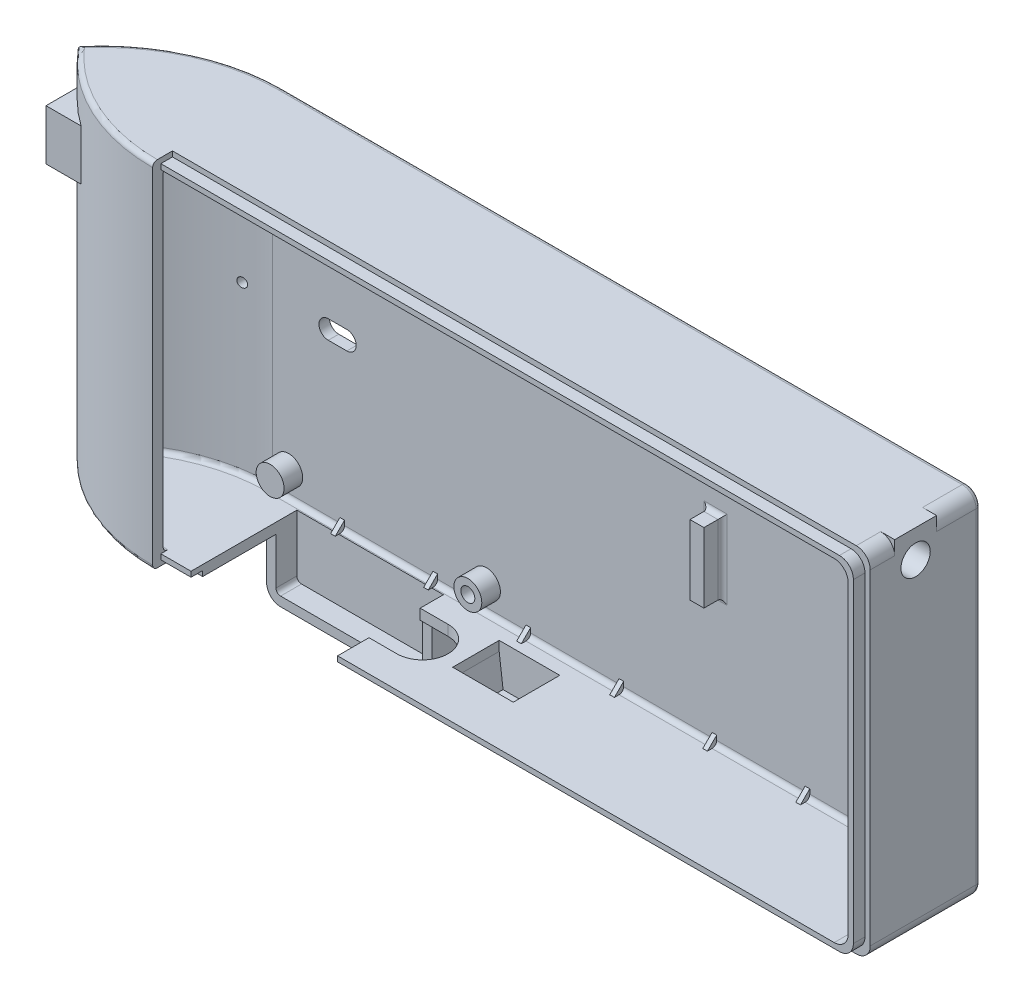
SolidWorks part; units mm, degrees
ref_plane "Front Plane" through (0, 0, 0) normal (0, 0, 1) x (1, 0, 0)
ref_plane "Top Plane" through (0, 0, 0) normal (0, 1, 0) x (1, 0, 0)
ref_plane "Right Plane" through (0, 0, 0) normal (1, 0, 0) x (0, 0, -1)
sketch "Sketch1" plane through (0, 0, 0) normal (0, 1, 0) x (1, 0, 0)
  line L0 (0, 14) -> (-30, 14) construction
  line L1 (0, 0) -> (150, 0)
  line L2 (0, 0) -> (0, 28) construction
  line L3 (0, 28) -> (150, 28)
  line L4 (150, 0) -> (150, 28)
  line L5 (0, 0) -> (150, 28) construction
  line L6 (0, 28) -> (150, 0) construction
  arc A0 (-30, 14) -> (0, 28) centre (0, -11.1429) cw
  arc A1 (-30, 14) -> (0, 0) centre (0, 39.1429) ccw
  point P4 (75, 14)
  point P9 (0, 14)
  dimension "D1" = 30
  dimension "D2" = 28
  dimension "D3" = 150
extrude "Boss-Extrude1" add sketch "Sketch1" along normal blind 38
sketch "Sketch3" plane through (0, 0, 0) normal (0, -1, 0) x (1, 0, 0)
  line L8 (0, -2.25) -> (0, 0)
  line L9 (0, 0) -> (147.75, 0)
  line L10 (0, 0) -> (150, 0) construction
  line L11 (147.75, -25.75) -> (147.75, -2.25)
  line L12 (0, -25.75) -> (147.75, -25.75)
  line L13 (147.75, -2.25) -> (0, -2.25)
  line L15 (0, -25.75) -> (147.75, -25.75)
  line L18 (147.75, 0) -> (147.75, -25.75)
  arc A9 (-26.9985, -14) -> (0, -25.75) centre (0, 11.1429) ccw
  arc A10 (0, -2.25) -> (-26.9985, -14) centre (0, -39.1429) ccw
  arc A11 (-26.9985, -14) -> (0, -25.75) centre (0, 11.1429) ccw
  arc A12 (0, -2.25) -> (-26.9985, -14) centre (0, -39.1429) ccw
  dimension "D1" = 2.25
extrude "Cut-Extrude1" cut sketch "Sketch3" against normal blind 35.75
ref_plane "Plane1" through (75, 0, 0) normal (1, 0, 0) x (0, 0, -1)
sketch "Sketch4" plane through (75, 0, 0) normal (1, 0, 0) x (0, 0, -1)
  line L0 (23.75, 35.75) -> (25.75, 33.75)
  line L1 (14, 35.75) -> (25.75, 35.75) construction
  line L2 (25.75, 35.75) -> (25.75, 0) construction
  dimension "D1" = 2
  dimension "D2" = 2
rib "Rib6" sketch "Sketch4" sketch "Sketch4" thickness 1 extrusion direction parallel to sketch draft on no parameters "D1"=1
pattern_linear "LPattern2" count 4 spacing 20 along (-1, 0, 0) count 4 spacing 20 along (1, 0, 0) of "Rib6" pattern seed only yes
ref_plane "Plane2" through (0, 20, 0) normal (0, -1, 0) x (-1, 0, 0)
sketch "Sketch5" plane through (0, 20, 0) normal (0, -1, 0) x (1, 0, 0)
  line L0 (145.75, -25.75) -> (147.75, -23.75)
  line L1 (0, -25.75) -> (147.75, -25.75) construction
  line L2 (147.75, -25.75) -> (147.75, 0) construction
  line L3 (135.5, -25.75) -> (147.75, -25.75) construction
  dimension "D1" = 2
  dimension "D2" = 2
rib "Rib8" sketch "Sketch5" sketch "Sketch5" thickness 1 extrusion direction parallel to sketch draft on no parameters "D1"=1
mirror "Mirror1" about plane through (0, 0, -39.1429) normal (0, 1, 0) of bodies 103
sketch "Sketch7" plane through (0, 0, 0) normal (0, 0, 1) x (1, 0, 0)
  line L5 (0, 38) -> (150, 38)
  line L6 (150, 38) -> (150, -38)
  line L9 (150, -38) -> (0, -38)
  line L15 (0, -38) -> (0, -36.875)
  line L16 (0, -38) -> (0, -35.75) construction
  line L17 (0, -36.875) -> (148.875, -36.875)
  line L18 (148.875, -36.875) -> (148.875, 36.875)
  line L19 (148.875, 36.875) -> (0, 36.875)
  line L20 (0, 38) -> (0, 35.75) construction
  line L22 (0, 38) -> (0, 36.875)
  dimension "D1" = 1.125
  dimension "D2" = 1.125
  dimension "0.8" = 1.125
extrude "Clam shell lip" cut sketch "Sketch7" against normal blind 4.25
fillet "Fillet7" radius 3 6 edges at (147.75, 35.75, -12.875) (150, 38, -16.125) (150, -38, -16.125) (147.75, -35.75, -12.875) (148.875, -36.875, -2.125) (148.875, 36.875, -2.125)
sketch "Sketch9" plane through (0, 0, 0) normal (0, 0, 1) x (1, 0, 0)
  line L0 (0, -38) -> (147, -38) construction
  line L1 (0, 38) -> (150, 38)
  line L2 (0, 38) -> (0, -38)
  line L3 (0, -38) -> (150, -38)
  line L4 (150, 38) -> (150, -38)
  line L5 (0, 38) -> (150, -38) construction
  line L6 (0, -38) -> (150, 38) construction
  line L7 (150, -35) -> (150, 35) construction
  line L8 (147, 38) -> (0, 38) construction
  point P4 (75, 0)
extrude "Cut-Extrude4" cut sketch "Sketch9" against normal blind 1.75
sketch "Sketch10" plane through (150, 0, 0) normal (1, 0, 0) x (0, 0, -1)
  line L0 (28, 35) -> (28, -35) construction
  line L1 (4.25, 38) -> (28, 38) construction
  line L2 (9.5, 32) -> (9.5, 38)
  line L3 (9.5, 38) -> (18.5, 38)
  line L4 (18.5, 38) -> (18.5, 32)
  arc A0 (9.5, 32) -> (18.5, 32) centre (14, 32) ccw
  dimension "D1" = 9
  dimension "D2" = 14
  dimension "D3" = 6
extrude "Arrow Shaft Extrude" add sketch "Sketch10" against normal blind 50
sketch "Sketch11" plane through (150, 0, 0) normal (1, 0, 0) x (0, 0, -1)
  circle A0 centre (14, 32) radius 3.15
  dimension "D1" = 6.3
extrude "Arrow Shaft Ex-Cut" cut sketch "Sketch11" against normal up to surface (50 mm away) up to face at (100, 32.75, -14)
sketch "Sketch12" plane through (0, 0, -25.75) normal (0, 0, 1) x (1, 0, 0)
  line L0 (35.5, -35.75) -> (54.5, -35.75) construction
  line L1 (0, 35.75) -> (0, -35.75) construction
  line L2 (3.5, 19.66) -> (3.5, -30.34) construction
  line L3 (3.5, -30.34) -> (46, -30.34) construction
  line L4 (3.5, 19.66) -> (78.5, 19.66) construction
  circle A0 centre (46, -30.34) radius 1.5
  circle A1 centre (3.5, 19.66) radius 1.5
  circle A2 centre (46, -30.34) radius 3
  circle A3 centre (3.5, 19.66) radius 3
  circle A4 centre (3.5, -30.34) radius 3
  circle A5 centre (78.5, 19.66) radius 3
  dimension "D1" = 3
  dimension "D3" = 6
  dimension "D2" = 5.41
  dimension "D4" = 42.5
  dimension "D5" = 50
  dimension "D6" = 46
  dimension "D7" = 75
extrude "PCB Studs" add sketch "Sketch12" along normal blind 4
sketch "Sketch13" plane through (0, -38, 0) normal (0, -1, 0) x (1, 0, 0)
  line L1 (6.5, -1.75) -> (38, -1.75)
  line L2 (6.5, -1.75) -> (6.5, -24.5)
  line L3 (6.5, -24.5) -> (38, -24.5)
  line L4 (38, -1.75) -> (38, -8.5)
  line L5 (6.5, -1.75) -> (38, -24.5) construction
  line L6 (6.5, -24.5) -> (38, -1.75) construction
  line L7 (0, -4.25) -> (0, 0) construction
  line L8 (147, -28) -> (0, -28) construction
  line L9 (-30, -14) -> (150, -14) construction
  line L10 (150, -4.25) -> (150, -28) construction
  line L11 (44, -8.5) -> (38, -8.5)
  line L12 (44, -19.5) -> (38, -19.5)
  line L13 (38, -19.5) -> (38, -24.5)
  line L14 (0, -1.75) -> (145.875, -1.75) construction
  arc A0 (44, -19.5) -> (44, -8.5) centre (44, -14) ccw
  point P4 (22.25, -13.125)
  dimension "D4" = 11
  dimension "D1" = 6.5
  dimension "D2" = 3.5
  dimension "D3" = 31.5
  dimension "D5" = 6
extrude "SHT-PCB " cut sketch "Sketch13" against normal up to surface (2.25 mm away) up to face at (69.4134, -35.75, -22.4779)
sketch "Sketch14" plane through (0, -38, 0) normal (0, -1, 0) x (1, 0, 0)
  line L5 (147, -28) -> (0, -28) construction
  line L6 (4.5, -20) -> (40, -20)
  line L9 (4.5, -20) -> (4.5, -28)
  line L10 (4.5, -28) -> (40, -28)
  line L11 (40, -20) -> (40, -28)
  line L12 (4.5, -20) -> (40, -28) construction
  line L13 (4.5, -28) -> (40, -20) construction
  line L14 (38, -24.5) -> (38, -19.5) construction
  line L15 (6.5, -4.25) -> (6.5, -24.5) construction
  point P4 (22.25, -24)
  dimension "D1" = 8
  dimension "D2" = 2
  dimension "D3" = 2
extrude "PCB extension" add sketch "Sketch14" along normal blind 13
fillet "Fillet1" radius 3 2 edges at (40, -51, -24) (4.5, -51, -24)
sketch "Sketch15" plane through (0, 0, -20) normal (0, 0, 1) x (1, 0, 0)
  line L0 (6.5, -40) -> (6.5, -38)
  line L1 (38, -40) -> (38, -38)
  line L2 (38, -38) -> (6.5, -38)
  line L12 (7.5, -49) -> (37, -49)
  line L13 (38, -48) -> (38, -40)
  line L14 (38, -40) -> (6.5, -40)
  line L15 (6.5, -40) -> (6.5, -48)
  line L16 (7.5, -49) -> (37, -49)
  line L17 (38, -48) -> (38, -40)
  line L19 (6.5, -40) -> (6.5, -48)
  arc A4 (37, -49) -> (38, -48) centre (37, -48) ccw
  arc A5 (6.5, -48) -> (7.5, -49) centre (7.5, -48) ccw
  arc A6 (37, -49) -> (38, -48) centre (37, -48) ccw
  arc A7 (6.5, -48) -> (7.5, -49) centre (7.5, -48) ccw
  dimension "D1" = 2
extrude "Cut-Extrude7" cut sketch "Sketch15" against normal up to surface (4.5 mm away) up to face at (23.625, -36.3125, -24.5)
ref_plane "Plane3" through (-30, 0, 0) normal (1, 0, 0) x (0, 0, -1)
sketch "Sketch16" plane through (-30, 0, 0) normal (1, 0, 0) x (0, 0, -1)
  line L0 (14, 38) -> (14, -38) construction
  line L1 (18.925, 28) -> (9.075, 28)
  line L2 (18.925, 28) -> (18.925, 21.15)
  line L3 (18.925, 21.15) -> (9.075, 21.15)
  line L4 (9.075, 28) -> (9.075, 21.15)
  line L5 (18.925, 28) -> (9.075, 21.15) construction
  line L6 (18.925, 21.15) -> (9.075, 28) construction
  line L7 (14, 38) -> (0, 38) construction
  point P4 (14, 24.575)
  dimension "D1" = 9.85
  dimension "D2" = 6.85
  dimension "D3" = 10
extrude "Anemometer Shaft" cut sketch "Sketch16" along normal blind 10
sketch "Sketch17" plane through (-30, 0, 0) normal (1, 0, 0) x (0, 0, -1)
  line L6 (14, 38) -> (14, 28) construction
  line L7 (20.925, 30) -> (7.075, 30)
  line L8 (20.925, 30) -> (20.925, 19.15)
  line L9 (20.925, 19.15) -> (7.075, 19.15)
  line L10 (7.075, 30) -> (7.075, 19.15)
  line L11 (20.925, 30) -> (7.075, 19.15) construction
  line L12 (20.925, 19.15) -> (7.075, 30) construction
  line L13 (14, 28) -> (18.925, 28) construction
  line L14 (18.925, 28) -> (18.925, 21.15) construction
  line L15 (14, 21.15) -> (9.075, 21.15) construction
  line L16 (9.075, 21.15) -> (9.075, 28) construction
  line L18 (18.925, 28) -> (9.075, 28)
  line L19 (18.925, 28) -> (18.925, 21.15)
  line L20 (18.925, 21.15) -> (9.075, 21.15)
  line L21 (9.075, 28) -> (9.075, 21.15)
  line L22 (18.925, 28) -> (9.075, 21.15) construction
  line L23 (18.925, 21.15) -> (9.075, 28) construction
  point P14 (14, 24.575)
  point P19 (14, 24.575)
  dimension "D1" = 2
  dimension "D2" = 2
  dimension "D3" = 2
  dimension "D4" = 2
extrude "Anemometer Extrude" add sketch "Sketch17" along normal blind 10
ref_plane "Plane4" through (0, 0, -13) normal (0, 0, -1) x (-1, 0, 0)
sketch "Sketch19" plane through (0, 0, -13) normal (0, 0, -1) x (-1, 0, 0)
  line L0 (-51, -38) -> (-52, -46)
  line L1 (-147, -38) -> (-40, -38) construction
  line L2 (-52, -46) -> (-66, -46)
  line L3 (-66, -46) -> (-67, -38)
  line L4 (-67, -38) -> (-51, -38)
  line L5 (0, 38) -> (0, -38) construction
  point P6 (-59, -46)
  point P7 (-59, -38)
  dimension "D1" = 16
  dimension "D2" = 51
  dimension "D3" = 8
  dimension "D4" = 14
extrude "5V booster belly" add sketch "Sketch19" along normal blind 10 and the other way blind 2
sketch "Sketch20" plane through (0, 0, -13) normal (0, 0, -1) x (-1, 0, 0)
  line L14 (-65.5116, -37.8139) -> (-65.5116, -32.8139)
  line L15 (-65.5116, -32.8139) -> (-52.4884, -32.8139)
  line L16 (-52.4884, -32.8139) -> (-52.4884, -37.8139)
  line L17 (-53.3242, -44.5) -> (-52.4884, -37.8139)
  line L18 (-65.5116, -37.8139) -> (-64.6758, -44.5)
  line L19 (-64.6758, -44.5) -> (-53.3242, -44.5)
  line L20 (-53.3242, -44.5) -> (-52.4884, -37.8139)
  line L21 (-65.5116, -37.8139) -> (-64.6758, -44.5)
  line L22 (-64.6758, -44.5) -> (-53.3242, -44.5)
  dimension "D2" = 5
  dimension "D1" = 1.5
extrude "5V booster cutout" cut sketch "Sketch20" against normal blind 1 and the other way blind 9
fillet "Fillet2" radius 2 8 edges at (66.5, -42, -23) (59, -46, -23) (51.5, -42, -23) (52, -46, -17) (51.5, -42, -11) (59, -46, -11) (66.5, -42, -11) (66, -46, -17)
sketch "Sketch21" plane through (0, 0, -28) normal (0, 0, -1) x (-1, 0, 0)
  line L0 (0, 38) -> (0, -38) construction
  line L1 (0, 5) -> (30, 5)
  line L2 (0, 5) -> (0, -5)
  line L3 (0, -5) -> (30, -5)
  line L4 (30, 5) -> (30, -5)
  line L5 (0, 5) -> (30, -5) construction
  line L6 (0, -5) -> (30, 5) construction
  line L7 (30, 19.15) -> (30, -38) construction
  point P4 (15, 0)
  point P9 (0, 0)
  dimension "D1" = 10
extrude "Thermocouple Mount" add sketch "Sketch21" along direction (0, 0, -1) on the side against the normal up to surface (14 mm away) up to face at (-21.0566, 12.2875, -20.1253)
sketch "Sketch23" plane through (0, 0, -25.75) normal (0, 0, 1) x (1, 0, 0)
  line L0 (150, -35) -> (150, 35) construction
  line L1 (93.75, 7.5) -> (96.75, 7.5)
  line L2 (93.75, 7.5) -> (93.75, -7.5)
  line L3 (93.75, -7.5) -> (96.75, -7.5)
  line L4 (96.75, 7.5) -> (96.75, -7.5)
  line L5 (93.75, 7.5) -> (96.75, -7.5) construction
  line L6 (93.75, -7.5) -> (96.75, 7.5) construction
  line L7 (147.75, 19.5) -> (147.75, -19.5) construction
  point P4 (95.25, 0)
  point P8 (150, 0)
  point P9 (96.75, 0)
  dimension "D1" = 3
  dimension "D2" = 15
  dimension "D3" = 51
extrude "Battery Wall" add sketch "Sketch23" along normal blind 4
sketch "Sketch22" plane through (0, 0, -28) normal (0, 0, -1) x (-1, 0, 0)
  line L0 (30, -5) -> (30, 5) construction
  line L1 (-12, 0) -> (-16, 0) construction
  line L2 (-12, -2) -> (-16, -2)
  line L3 (-12, 2) -> (-16, 2)
  circle A0 centre (6, 0) radius 1
  arc A1 (-12, -2) -> (-12, 2) centre (-12, 0) ccw
  arc A2 (-16, 2) -> (-16, -2) centre (-16, 0) ccw
  point P7 (-14, 0)
  dimension "D2" = 2
  dimension "D1" = 24
  dimension "D3" = 4
  dimension "D4" = 4
  dimension "20" = 20
extrude "Thermocouple Holes" cut sketch "Sketch22" against normal up to surface (2.9202 mm away) up to face at (-18.8505, 12.2875, -19.159)
fillet "Fillet3" radius 2 2 edges at (-16.5529, -5, -24.3277) (-16.5529, 5, -24.3277)
fillet "Fillet4" radius 1 51 edges at (-14.7223, -35.75, -22.6852) (-14.7223, 35.75, -22.6852) (7.25, -35.75, -25.75) (25, -35.75, -25.75) (45, -35.75, -25.75) (65, -35.75, -25.75) (85, -35.75, -25.75) (105, -35.75, -25.75) (125, -35.75, -25.75) (140.125, -35.75, -25.75) (7.25, 35.75, -25.75) (25, 35.75, -25.75) (45, 35.75, -25.75) (65, 35.75, -25.75) (85, 35.75, -25.75) (105, 35.75, -25.75) (125, 35.75, -25.75) (140.125, 35.75, -25.75) (147.75, 32.375, -18.5) (147.75, 27.5, -14) (147.75, 32.375, -9.5) (147.75, -26.625, -25.75) (147.75, 0, -25.75) (147.75, 26.625, -25.75) (-14.7223, -35.75, -5.3148) (-14.7223, 35.75, -5.3148) (2.25, -38, -28) (-16.5529, -38, -3.6723) (-16.5529, -38, -24.3277) (93.5, -38, -28) (73.5, 38, -28) (-16.5529, 38, -24.3277) (-16.5529, 38, -3.6723) (150, 0, -28) (40, -43, -28) (39.1213, -50.1213, -28) (22.25, -51, -28) (5.3787, -50.1213, -28) (4.5, -43, -28) (95.25, -7.5, -25.75) (93.75, 0, -25.75) (95.25, 7.5, -25.75) (96.75, 0, -25.75) (146.8713, 34.8713, -25.75) (122.375, 35.75, -9.5) (146.8713, 34.8713, -9.5) (122.375, 35.75, -18.5) (146.8713, 34.8713, -18.5) (149.1213, -37.1213, -28) (149.1213, 37.1213, -28) (146.8713, -34.8713, -25.75)
